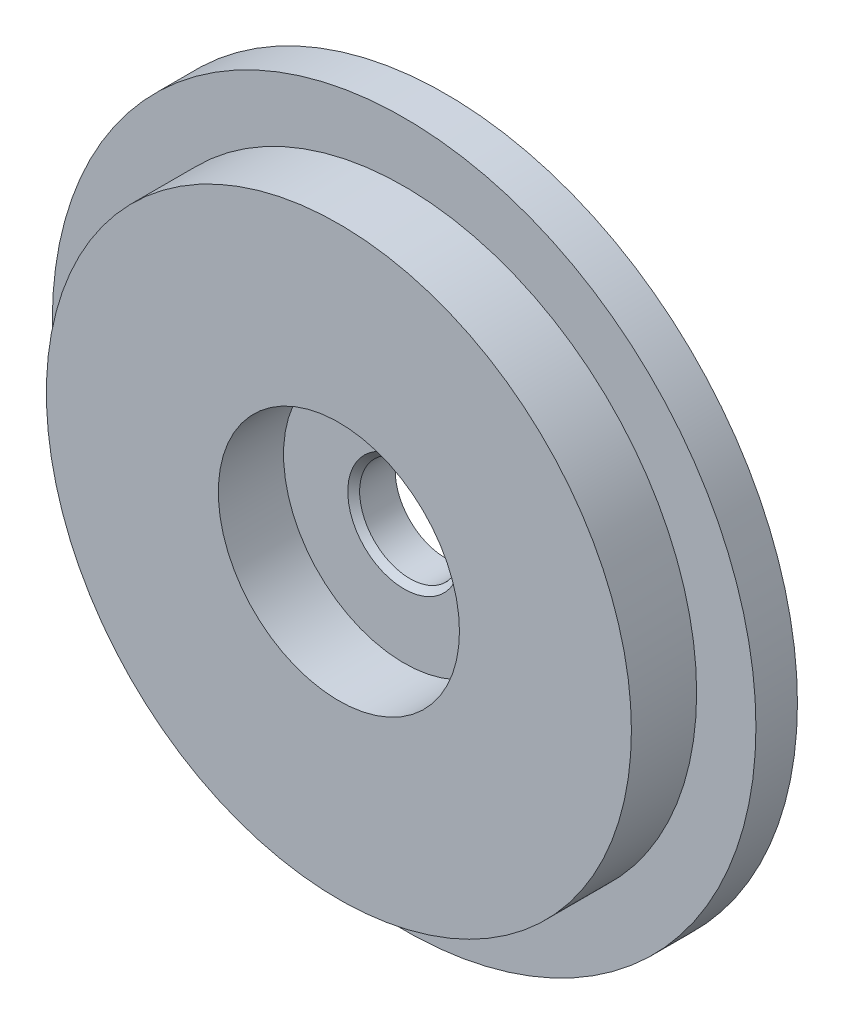
SolidWorks part; units mm, degrees
material "PA 类型 6"
ref_plane "前视基准面" through (0, 0, 0) normal (0, 0, 1) x (1, 0, 0)
ref_plane "上视基准面" through (0, 0, 0) normal (0, 1, 0) x (1, 0, 0)
ref_plane "右视基准面" through (0, 0, 0) normal (1, 0, 0) x (0, 0, -1)
sketch "草图1" plane through (0, 0, 0) normal (0, 0, 1) x (1, 0, 0)
  circle A0 centre (0, 0) radius 17.8
extrude "凸台-拉伸1" add sketch "草图1" along normal blind 2.1
sketch "草图2" plane through (0, 0, 0) normal (0, 0, 1) x (1, 0, 0)
  circle A0 centre (0, 0) radius 14.8
  circle A1 centre (0, 0) radius 6.1
extrude "凸台-拉伸2" add sketch "草图2" along normal blind 3.3 from surface starting at face at (17.8, 0, 2.1)
sketch "草图3" plane through (0, 0, 0) normal (0, 0, 1) x (1, 0, 0)
  circle A0 centre (0, 0) radius 2.55
extrude "切除-拉伸1" cut sketch "草图3" along normal up to next
chamfer "倒角1" distance 0.3 angle 45 1 edges at (2.55, 0, 2.1)
